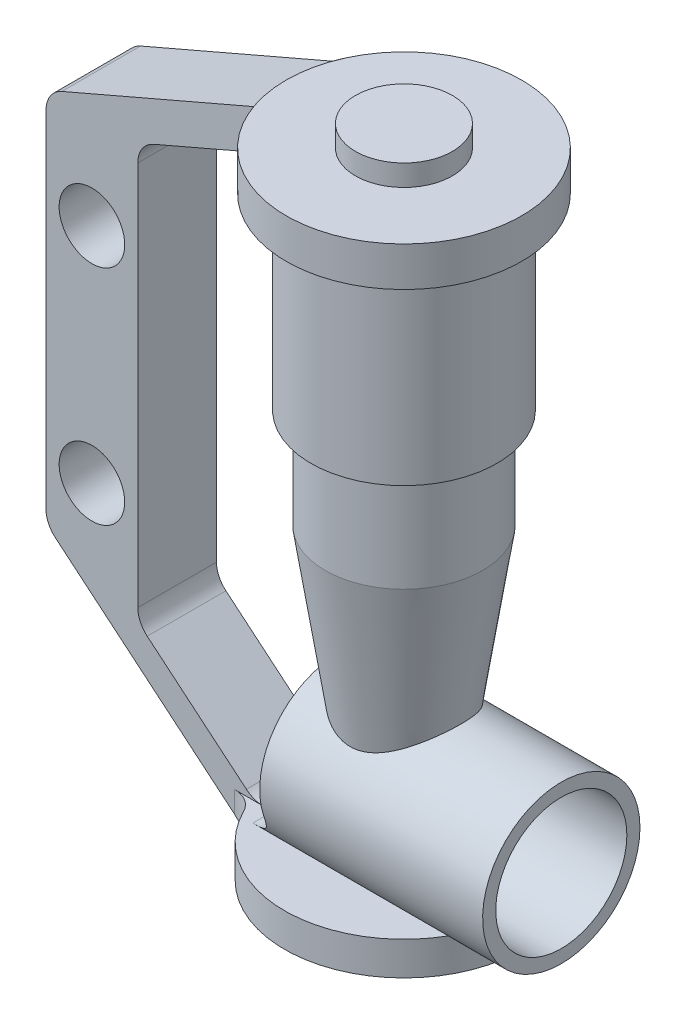
SolidWorks part; units mm, degrees
ref_plane "Front Plane" through (0, 0, 0) normal (0, 0, 1) x (1, 0, 0)
ref_plane "Top Plane" through (0, 0, 0) normal (0, 1, 0) x (1, 0, 0)
ref_plane "Right Plane" through (0, 0, 0) normal (1, 0, 0) x (0, 0, -1)
sketch "Sketch2" plane through (0, 0, 0) normal (0, 0, 1) x (1, 0, 0)
  line L0 (0, 47.4815) -> (0, -202.5185) construction
  line L1 (0, 47.4815) -> (18.4843, 47.4815)
  line L2 (18.4843, 47.4815) -> (18.4843, 39.3946)
  line L3 (18.4843, 39.3946) -> (44.8721, 39.3946)
  line L4 (44.8721, 39.3946) -> (44.8721, 24.3464)
  line L5 (44.8721, 24.3464) -> (35.4459, 24.3464)
  line L6 (35.4459, 24.3464) -> (35.4459, -47.075)
  line L7 (35.4459, -47.075) -> (30.0077, -47.075)
  line L8 (30.0077, -47.075) -> (30.0077, -85.1422)
  line L9 (30.0077, -85.1422) -> (18.5463, -160.9367)
  line L10 (18.5463, -160.9367) -> (18.5463, -189.741)
  line L11 (18.5463, -189.741) -> (45.5176, -189.741)
  line L12 (45.5176, -189.741) -> (45.5176, -202.5185)
  line L13 (45.5176, -202.5185) -> (0, -202.5185)
  line L14 (0, 47.4815) -> (0, -202.5185)
  dimension "D1" = 250
revolve "Revolve1" add sketch "Sketch2" angle 360 about L0
sketch "Sketch3" plane through (0, 0, 0) normal (0, 0, 1) x (1, 0, 0)
  line L0 (-42.2853, 24.3464) -> (-86.4744, 5.2797)
  line L1 (-86.4744, 5.2797) -> (-86.4744, -152.7902)
  line L2 (-86.4744, -152.7902) -> (-42.2853, -189.741)
  line L3 (-42.2853, -189.741) -> (-42.2853, -202.5185)
  line L4 (-42.2853, -202.5185) -> (-44.0807, -202.5185)
  line L5 (-44.0807, -202.5185) -> (-121.4744, -137.8022)
  line L6 (-121.4744, -137.8022) -> (-121.4744, 5.2261)
  line L7 (-121.4744, 5.2261) -> (-42.2853, 39.3946)
  line L8 (-45.5176, -202.5185) -> (45.5176, -202.5185) construction
  line L9 (-42.2853, 24.3464) -> (-42.2853, 39.3946)
  line L10 (45.5176, -189.741) -> (-45.5176, -189.741) construction
  line L11 (44.8721, 39.3946) -> (-44.8721, 39.3946) construction
  line L12 (-44.8721, 24.3464) -> (44.8721, 24.3464) construction
  line L13 (-103.9744, -30.8053) -> (-103.9744, -115.8053) construction
  circle A0 centre (-103.9744, -30.8053) radius 12.5
  circle A1 centre (-103.9744, -115.8053) radius 12.5
  dimension "D2" = 25
  dimension "D4" = 25
  dimension "D1" = 35
  dimension "D3" = 17.5
  dimension "D5" = 85
extrude "Boss-Extrude1" add sketch "Sketch3" along normal blind 15 and the other way blind 15
sketch "Sketch4" plane through (0, 0, 0) normal (1, 0, 0) x (0, 0, -1)
  line L0 (0, 0) -> (0, -170) construction
  circle A0 centre (0, -170) radius 25
  circle A1 centre (0, -170) radius 30
  dimension "D1" = 50
  dimension "D2" = 60
  dimension "D3" = 170
extrude "Boss-Extrude2" add sketch "Sketch4" along normal blind 60
sketch "Sketch5" plane through (0, 0, 0) normal (1, 0, 0) x (0, 0, -1)
  line L0 (0, 0) -> (0, -170) construction
  circle A0 centre (0, -170) radius 30
  dimension "D2" = 60
  dimension "D1" = 170
extrude "Boss-Extrude3" add sketch "Sketch5" along normal blind 5 and the other way blind 25
fillet "Fillet1" radius 10 8 edges at (-42.975, -196.1297, 15) (-42.975, -196.1297, -15) (-121.4744, -137.8022, 0) (-121.4744, 5.2261, 0) (-86.4744, 5.2797, 0) (-86.4744, -152.7902, 0) (-42.2853, -189.741, 0) (-25, -189.741, 0)
sketch "Sketch6" plane through (60, 0, 0) normal (1, 0, 0) x (0, 0, -1)
  circle A0 centre (0, -170) radius 25
  dimension "D2" = 50
  dimension "D1" = 170
extrude "Cut-Extrude1" cut sketch "Sketch6" against normal blind 65
